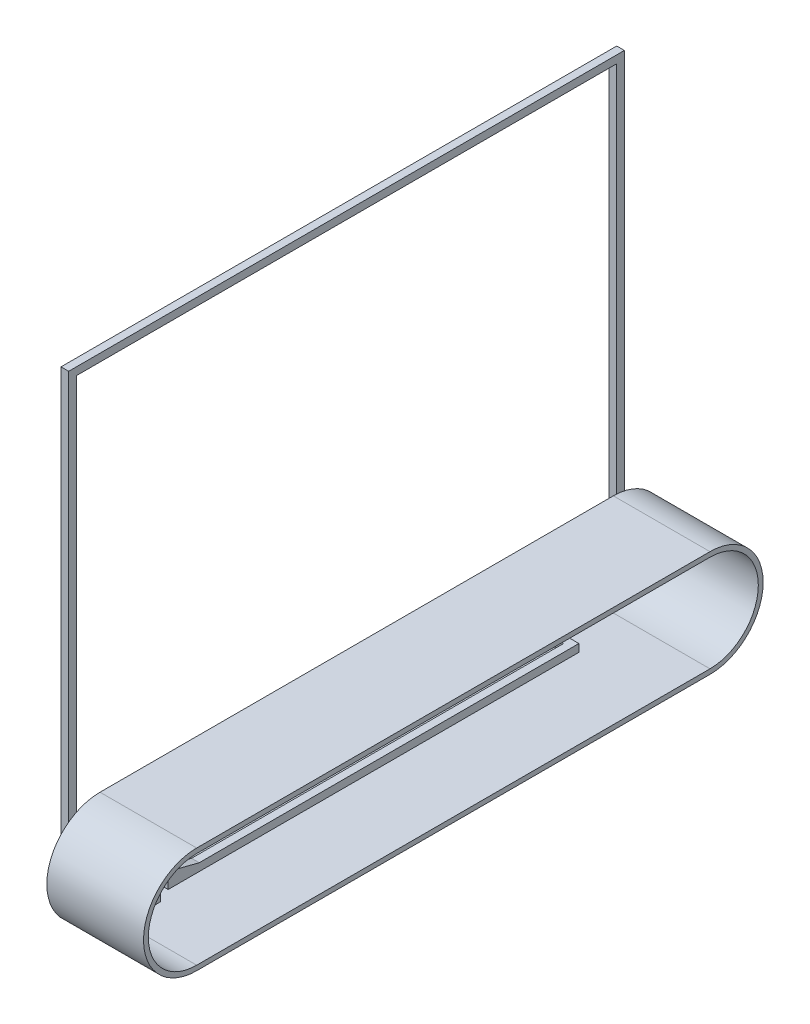
SolidWorks part; units mm, degrees
ref_plane "Front Plane" through (0, 0, 0) normal (0, 0, 1) x (1, 0, 0)
ref_plane "Top Plane" through (0, 0, 0) normal (0, 1, 0) x (1, 0, 0)
ref_plane "Right Plane" through (0, 0, 0) normal (1, 0, 0) x (0, 0, -1)
sketch "Sketch1" plane through (0, 0, 0) normal (1, 0, 0) x (0, 0, -1)
  line L0 (-559.125, -472.0175) -> (-559.125, 472.0175)
  line L2 (-575, -487.8925) -> (-575, 487.8925)
  line L3 (-575, 487.8925) -> (575, 487.8925)
  line L4 (575, -487.8925) -> (575, 487.8925)
  line L5 (-575, -487.8925) -> (575, 487.8925) construction
  line L6 (-575, 487.8925) -> (575, -487.8925) construction
  line L7 (-559.125, 472.0175) -> (559.125, 472.0175)
  line L8 (559.125, -472.0175) -> (559.125, 472.0175)
  line L9 (-575, -487.8925) -> (-559.125, -487.8925)
  line L10 (559.125, -487.8925) -> (575, -487.8925)
  line L11 (-559.125, -487.8925) -> (559.125, -487.8925)
  line L12 (-559.125, -472.0175) -> (559.125, -472.0175)
  line L14 (559.125, -487.8925) -> (559.125, 472.0175) construction
  line L15 (-559.125, -487.8925) -> (-559.125, 472.0175) construction
  point P0 (0, 0)
  point P7 (0, 0)
  dimension "D1" = 1150
  dimension "D2" = 975.785
  dimension "D4" = 15.875
  dimension "D3" = 15.875
extrude "Boss-Extrude1" add sketch "Sketch1" along normal blind 15.875
sketch "Sketch2" plane through (15.875, 0, 0) normal (1, 0, 0) x (0, 0, -1)
  line L1 (-425, -487.8925) -> (-409.125, -487.8925)
  line L2 (-425, -487.8925) -> (-425, -472.0175)
  line L3 (-425, -472.0175) -> (-409.125, -472.0175)
  line L4 (-409.125, -487.8925) -> (-409.125, -472.0175)
  line L10 (-559.125, -472.0175) -> (559.125, -472.0175) construction
  line L11 (-575, 487.8925) -> (-575, -487.8925) construction
  line L12 (0, 8.7312) -> (0, -8.7312) construction
  line L13 (425, -472.0175) -> (409.125, -472.0175)
  line L14 (409.125, -487.8925) -> (409.125, -472.0175)
  line L15 (425, -487.8925) -> (409.125, -487.8925)
  line L16 (425, -487.8925) -> (425, -472.0175)
  dimension "D1" = 15.875
  dimension "D3" = 150
  dimension "D4" = 15.875
extrude "Boss-Extrude2" add sketch "Sketch2" along normal blind 55.785
sketch "Sketch3" plane through (0, 0, 425) normal (0, 0, 1) x (1, 0, 0)
  line L7 (15.875, 487.8925) -> (15.875, -487.8925) construction
  line L8 (55.875, -472.0175) -> (71.75, -472.0175)
  line L9 (55.875, -472.0175) -> (55.875, -487.8925)
  line L10 (55.875, -487.8925) -> (71.75, -487.8925)
  line L11 (71.75, -472.0175) -> (71.75, -487.8925)
  line L12 (71.66, -472.0175) -> (15.875, -472.0175) construction
  dimension "40" = 40
  dimension "D2" = 15.875
  dimension "D5" = 15.875
extrude "Boss-Extrude3" add sketch "Sketch3" against normal up to surface (850 mm away) up to face at (43.7675, -479.955, -425)
sketch "Sketch4" plane through (15.875, 0, 0) normal (1, 0, 0) x (0, 0, -1)
  line L0 (425, -487.8925) -> (-425, -487.8925) construction
  line L1 (425, -487.8925) -> (-425, -487.8925)
  line L2 (-531.125, -387.8925) -> (531.125, -387.8925) construction
  line L3 (-531.125, -287.8925) -> (531.125, -287.8925)
  line L4 (-531.125, -487.8925) -> (531.125, -487.8925)
  arc A0 (-531.125, -287.8925) -> (-531.125, -487.8925) centre (-531.125, -387.8925) ccw
  arc A1 (531.125, -487.8925) -> (531.125, -287.8925) centre (531.125, -387.8925) ccw
  point P4 (0, -387.8925)
  dimension "D1" = 100
  dimension "D2" = 1062.25
extrude "Extrude-Thin2" add sketch "Sketch4" along normal blind 200 from offset 21 thin contours L4 A1 L3 A0 thin type one direction wall 10
sketch "Sketch5" plane through (15.875, 0, 0) normal (1, 0, 0) x (0, 0, -1)
  line L0 (-575, 487.8925) -> (-575, -487.8925) construction
  line L1 (-575, -337.8925) -> (-559.125, -337.8925)
  line L2 (-575, -337.8925) -> (-575, -437.8925)
  line L3 (-575, -437.8925) -> (-559.125, -437.8925)
  line L4 (-559.125, -337.8925) -> (-559.125, -437.8925)
  line L5 (-559.125, 472.0175) -> (-559.125, -472.0175) construction
  line L6 (-531.125, -287.8925) -> (-531.125, -487.8925) construction
  line L7 (-575, -487.8925) -> (-425, -487.8925) construction
  arc A4 (-531.125, -287.8925) -> (-531.125, -487.8925) centre (-531.125, -387.8925) ccw construction
  point P19 (-575, -387.8925)
  point P20 (-531.125, -387.8925)
  dimension "D1" = 100
extrude "Boss-Extrude4" add sketch "Sketch5" along normal blind 120
sketch "Sketch7" plane through (135.875, 0, 0) normal (1, 0, 0) x (0, 0, -1)
  line L2 (-559.125, -337.8925) -> (-505.125, -337.8925)
  line L3 (-559.125, -337.8925) -> (-559.125, -437.8925)
  line L4 (-559.125, -437.8925) -> (-505.125, -437.8925)
  line L5 (-505.125, -337.8925) -> (-505.125, -437.8925)
  circle A0 centre (-531.125, -387.8925) radius 15
  point P2 (-559.125, -387.8925)
  dimension "D1" = 30
  dimension "D2" = 28
  dimension "D3" = 54
extrude "Boss-Extrude5" add sketch "Sketch7" against normal blind 20
sketch "Sketch9" plane through (71.75, 0, 0) normal (1, 0, 0) x (0, 0, -1)
  line L0 (-425, -472.0175) -> (-360.617, -472.0175)
  line L1 (425, -472.0175) -> (-425, -472.0175) construction
  line L2 (-360.617, -472.0175) -> (-559.125, -421.5117)
  line L3 (-559.125, -421.5117) -> (-559.125, -437.8925)
  line L4 (-559.125, -437.8925) -> (-425, -472.0175)
  line L5 (-559.125, 472.0175) -> (-559.125, -337.8925) construction
  line L6 (-575, -437.8925) -> (-505.125, -437.8925) construction
  point P9 (0, 0)
  dimension "D1" = 15.875
extrude "Boss-Extrude6" add sketch "Sketch9" against normal up to surface (15.875 mm away) up to face at (55.875, -479.955, 0)
sketch "Sketch11" plane through (0, 0, 559.125) normal (0, 0, -1) x (-1, 0, 0)
  line L0 (-115.875, -337.8925) -> (-115.875, -437.8925) construction
  line L1 (-115.875, -422.0175) -> (-15.875, -422.0175)
  line L2 (-115.875, -422.0175) -> (-115.875, -353.7675)
  line L3 (-115.875, -353.7675) -> (-15.875, -353.7675)
  line L4 (-15.875, -422.0175) -> (-15.875, -353.7675)
  line L5 (-15.875, 472.0175) -> (-15.875, -337.8925) construction
  line L6 (-115.875, -337.8925) -> (-15.875, -337.8925) construction
  line L7 (-55.875, -437.8925) -> (-15.875, -437.8925) construction
  dimension "D1" = 15.875
  dimension "D2" = 15.875
extrude "Cut-Extrude1" cut sketch "Sketch11" against normal blind 20
